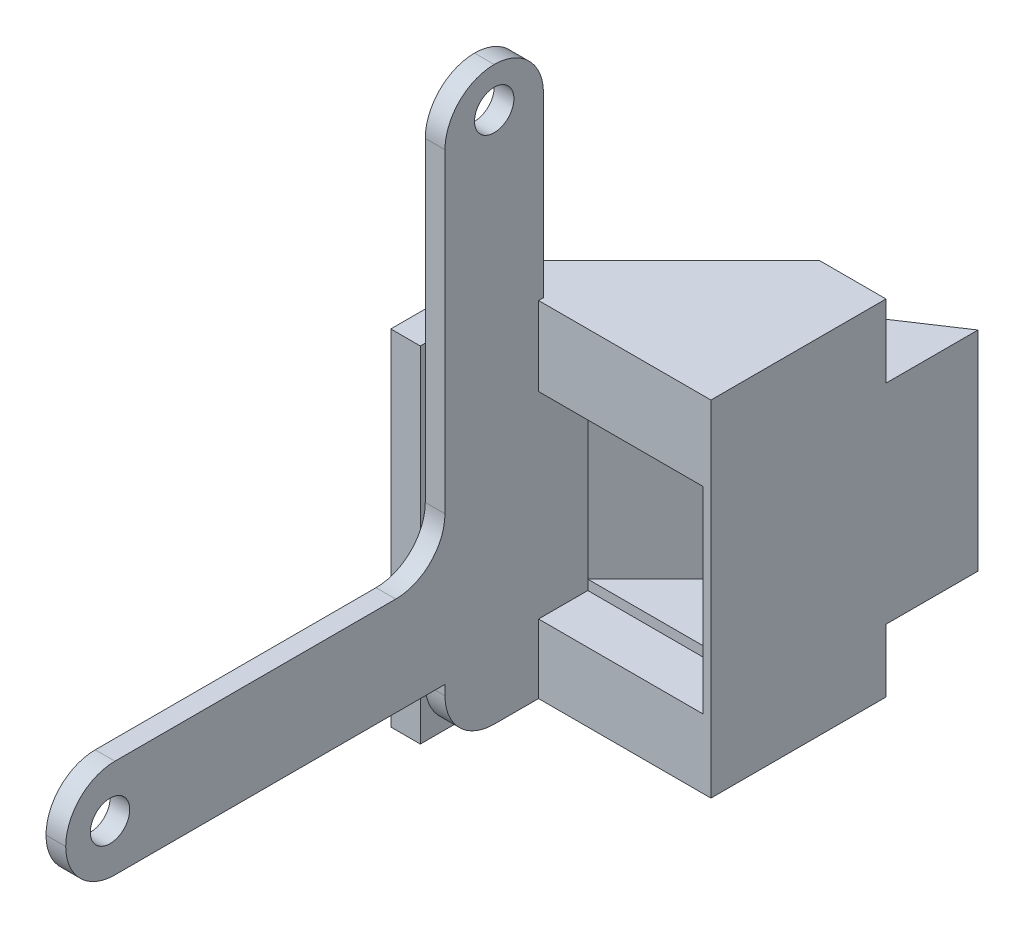
SolidWorks part; units mm, degrees
ref_plane "Спереди" through (0, 0, 0) normal (0, 0, 1) x (1, 0, 0)
ref_plane "Сверху" through (0, 0, 0) normal (0, 1, 0) x (1, 0, 0)
ref_plane "Справа" through (0, 0, 0) normal (1, 0, 0) x (0, 0, -1)
sketch "Эскиз1" plane through (0, 0, 0) normal (0, 0, 1) x (1, 0, 0)
  line L1 (0, 0) -> (2, 0)
  line L2 (0, 0) -> (0, -58)
  line L3 (0, -58) -> (2, -58)
  line L4 (2, 0) -> (2, -58)
  dimension "D1" = 2
  dimension "D2" = 58
extrude "Бобышка-Вытянуть1" add sketch "Эскиз1" along normal blind 53
sketch "Эскиз4" plane through (0, 0, 0) normal (-1, 0, 0) x (0, 0, 1)
  line L0 (5, -58) -> (5, -23)
  line L1 (5, -23) -> (0, -23)
  line L3 (5, -58) -> (0, -58)
  line L4 (0, -23) -> (0, -58)
  dimension "D1" = 35
  dimension "D2" = 5
extrude "Бобышка-Вытянуть3" add sketch "Эскиз4" against normal blind 19.5
sketch "Эскиз9" plane through (19.5, 0, 0) normal (1, 0, 0) x (0, 0, -1)
  line L0 (-5, -58) -> (-5, -23) construction
  line L2 (-5, -51) -> (0, -51)
  line L4 (-5, -51) -> (-5, -31)
  line L5 (-5, -31) -> (0, -31)
  line L6 (0, -51) -> (0, -31)
  line L7 (0, -23) -> (0, -58) construction
  line L8 (0, -58) -> (-5, -58) construction
  dimension "D1" = 20
  dimension "D2" = 7
extrude "Вырез-Вытянуть5" cut sketch "Эскиз9" against normal up to surface (16.7 mm away) from offset 0.8 offset against normal yes
sketch "Эскиз10" plane through (2, 0, 0) normal (1, 0, 0) x (0, 0, -1)
  line L0 (-5, -51) -> (0, -51) construction
  line L1 (0, -23) -> (0, 0) construction
  circle A0 centre (-48.5, -47) radius 2
  circle A1 centre (-9.5, -4) radius 2
  dimension "D1" = 4
  dimension "D2" = 4
  dimension "D3" = 48.5
  dimension "D4" = 47
  dimension "D5" = 9.5
extrude "Вырез-Вытянуть6" cut sketch "Эскиз10" against normal blind 10
sketch "Эскиз11" plane through (2, 0, 0) normal (1, 0, 0) x (0, 0, -1)
  line L0 (0, -23) -> (0, 0)
  line L1 (0, 0) -> (-53, 0)
  line L2 (-53, 0) -> (-53, -42)
  line L3 (-53, -58) -> (-53, 0) construction
  line L4 (-53, -42) -> (-14.5, -42)
  line L5 (-14.5, -42) -> (-14.5, 0)
  line L9 (-53, -58) -> (-14.5, -58)
  line L10 (-53, -58) -> (-53, -52)
  line L11 (-53, -52) -> (-14.5, -52)
  line L12 (-14.5, -58) -> (-14.5, -52)
  line L13 (0, -23) -> (-4.5, -23)
  line L14 (0, -23) -> (0, 0)
  line L15 (0, 0) -> (-4.5, 0)
  line L16 (-4.5, -23) -> (-4.5, 0)
  circle A0 centre (-9.5, -4) radius 2 construction
  circle A1 centre (-48.5, -47) radius 2 construction
  line M11 (-53, -58) -> (-5, -58)
  line M18 (-5, -23) -> (0, -23)
  line M19 (0, -23) -> (0, 0)
  line M20 (0, 0) -> (-53, 0)
  line M21 (-53, 0) -> (-53, -58)
  dimension "D3" = 5
  dimension "D4" = 5
  dimension "D1" = 10
  dimension "D2" = 10
extrude "Вырез-Вытянуть7" cut sketch "Эскиз11" against normal blind 10 contours L12 L11 M11 M21 | L4 L5 L1 M21 | L16 M18 M19 M20
fillet "Скругление1" radius 5 6 edges at (1, -42, 14.5) (1, 0, 4.5) (1, 0, 14.5) (1, -58, 14.5) (1, -42, 53) (1, -52, 53)
sketch "Эскиз12" plane through (0, -58, 0) normal (0, -1, 0) x (1, 0, 0)
  line L0 (0, 0) -> (0, 15)
  line L1 (0, 9.5) -> (0, 0) construction
  line L2 (0, 15) -> (-15, 15)
  line L3 (-15, 15) -> (0, 0)
  dimension "D1" = 45
  dimension "D2" = 15
extrude "Бобышка-Вытянуть4" add sketch "Эскиз12" against normal blind 35
sketch3d "Трехмерный эскиз1" plane through (0, 0, 0) normal (0, 0, 1) x (1, 0, 0)
sketch "Эскиз13" plane through (0, -23, 0) normal (0, 1, 0) x (1, 0, 0)
  line L0 (0, 0) -> (19.5, 0)
  line L1 (19.5, 0) -> (19.5, 22.1113)
  line L2 (19.5, 22.1113) -> (12.7724, 17.6443)
  line L3 (12.7724, 17.6443) -> (12.7724, 12.7724)
  line L4 (12.7724, 12.7724) -> (0, 0)
  line L5 (-15, -15) -> (0, 0) construction
extrude "Бобышка-Вытянуть5" add sketch "Эскиз13" against normal up to vertex (35 mm away)
sketch "Эскиз14" plane through (2, 0, 0) normal (-1, 0, 0) x (0, 0, 1)
  line L1 (15.0305, -139.4041) -> (-2.6445, -139.4041)
  line L2 (15.0305, -139.4041) -> (15.0305, 33.9564)
  line L3 (15.0305, 33.9564) -> (-2.6445, 33.9564)
  line L4 (-2.6445, -139.4041) -> (-2.6445, 33.9564)
extrude "Вырез-Вытянуть9" cut sketch "Эскиз14" against normal blind 12 from vertex at 5
sketch "Эскиз15" plane through (0, -31, 0) normal (0, -1, 0) x (1, 0, 0)
  line L0 (14.1724, 0) -> (1.9799, 0)
  line L1 (18.1, 0) -> (14.1724, 0)
  line L2 (18.1, 0) -> (18.1, -24.0314)
  line L3 (18.1, -24.0314) -> (14.1724, -24.0314)
  line L4 (14.1724, 0) -> (14.1724, -24.0314)
  line L5 (1.9799, 0) -> (14.1724, -12.1925)
  line L6 (19.5, 5) -> (19.5, -22.1113) construction
  line L7 (12.7724, -17.6443) -> (12.7724, -12.7724) construction
  line L8 (-3, 3) -> (12.7724, -12.7724) construction
  line L10 (2, 0) -> (18.7, 0) construction
  line M2 (2, 0) -> (18.7, 0)
  dimension "D1" = 1.4
  dimension "D2" = 1.4
  dimension "D3" = 1.4
extrude "Вырез-Вытянуть10" cut sketch "Эскиз15" against normal offset from surface (18 mm away) 1 from offset 19 contours L4 L3 L2 M2 | L0 L5 L4 M2 up to face at (10.35, -31, 2.5)
sketch "Эскиз16" plane through (12.7724, 0, 0) normal (-1, 0, 0) x (0, 0, 1)
  line L0 (-21.1817, -50) -> (-18.5739, -50) construction
  line L1 (-12.7724, -23) -> (-32.0959, -23)
  line L2 (-12.7724, -23) -> (-12.7724, -30.4)
  line L3 (-12.7724, -30.4) -> (-32.0959, -30.4)
  line L4 (-32.0959, -23) -> (-32.0959, -30.4)
  line L5 (-12.7724, -58) -> (-35.2143, -58)
  line L6 (-12.7724, -58) -> (-12.7724, -51.6)
  line L7 (-12.7724, -51.6) -> (-35.2143, -51.6)
  line L8 (-35.2143, -58) -> (-35.2143, -51.6)
  dimension "D1" = 1.6
  dimension "D2" = 1.6
extrude "Вырез-Вытянуть11" cut sketch "Эскиз16" against normal blind 10
sketch "Эскиз8" plane through (0, 0, 0) normal (0.7071, 0, -0.7071) x (-0.7071, 0, -0.7071)
  line L0 (0, -53.25) -> (-1.134, -53.25)
  line L1 (0, -58) -> (0, -23) construction
  line L2 (-1.134, -53.25) -> (-1.701, -54.2321)
  line L3 (-1.701, -54.2321) -> (-3, -53.4821)
  line L4 (-3, -53.4821) -> (-2, -51.75)
  line L5 (-2, -51.75) -> (0, -51.75)
  line L6 (0, -51.75) -> (0, -53.25)
  line L7 (6.0267, -40.5) -> (-33.6038, -40.5) construction
  line L8 (0, -29.25) -> (0, -27.75)
  line L9 (-2, -29.25) -> (0, -29.25)
  line L10 (-3, -27.5179) -> (-2, -29.25)
  line L11 (-1.701, -26.7679) -> (-3, -27.5179)
  line L12 (-1.134, -27.75) -> (-1.701, -26.7679)
  line L13 (0, -27.75) -> (-1.134, -27.75)
  circle A0 centre (-2.3505, -53.8571) radius 0.75
  circle A1 centre (-2.3505, -27.1429) radius 0.75
  point P12 (0, -52.5)
  point P21 (0, -40.5)
  dimension "D1" = 2
  dimension "D2" = 2
  dimension "D3" = 120
  dimension "D4" = 1.5
  dimension "D5" = 12
extrude "Вырез-Вытянуть8" cut sketch "Эскиз8" against normal blind 43 and the other way blind 20 contours L12 A1 L10 L9 L8 L13 | A1 L11 | A1 L11 | L3 A0 | L3 A0 | A0 L2 L0 L6 L5 L4
